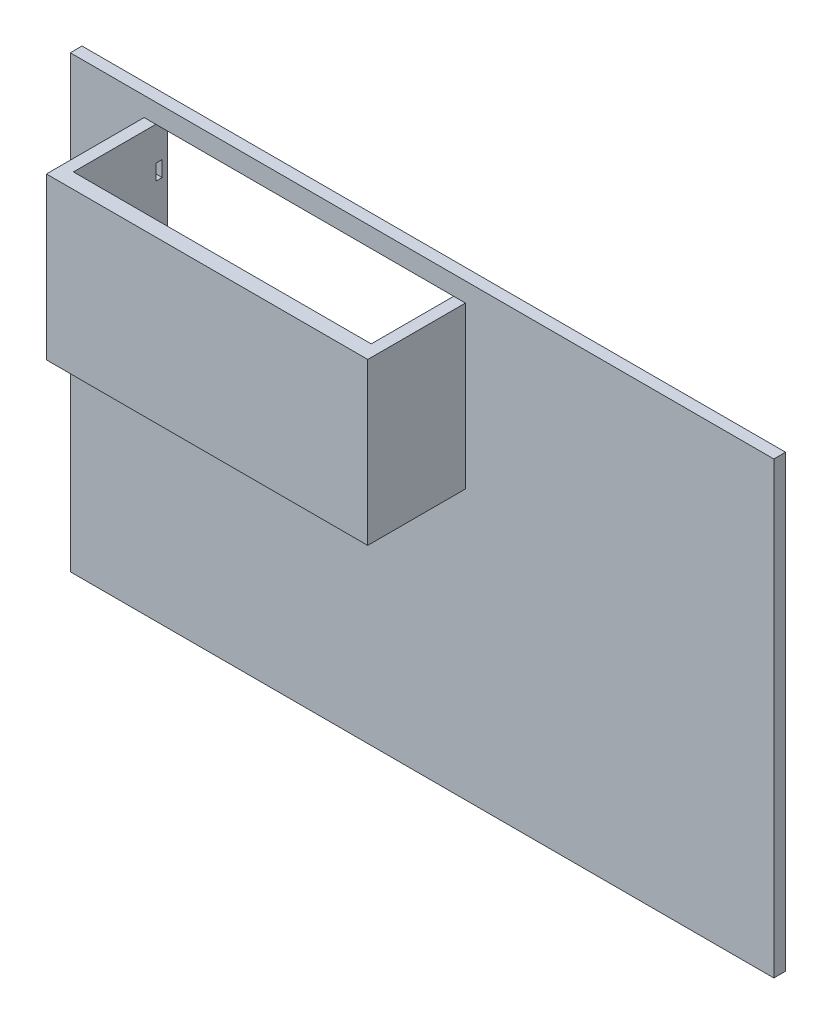
SolidWorks part; units mm, degrees
ref_plane "前视基准面" through (0, 0, 0) normal (0, 0, 1) x (1, 0, 0)
ref_plane "上视基准面" through (0, 0, 0) normal (0, 1, 0) x (1, 0, 0)
ref_plane "右视基准面" through (0, 0, 0) normal (1, 0, 0) x (0, 0, -1)
sketch "草图1" plane through (0, 0, 0) normal (0, 0, 1) x (1, 0, 0)
  line L1 (-90, 57.5) -> (90, 57.5)
  line L2 (-90, 57.5) -> (-90, -57.5)
  line L3 (-90, -57.5) -> (90, -57.5)
  line L4 (90, 57.5) -> (90, -57.5)
  line L5 (-90, 57.5) -> (90, -57.5) construction
  line L6 (-90, -57.5) -> (90, 57.5) construction
  point P0 (0, 0)
  dimension "D1" = 115
  dimension "D2" = 180
extrude "凸台-拉伸1" add sketch "草图1" along normal blind 3
sketch "草图7" plane through (0, 0, 0) normal (0, 0, -1) x (-1, 0, 0)
  line L0 (-90, 57.5) -> (90, 57.5) construction
  line L1 (-8.1, 52.6) -> (68.1, 52.6)
  line L2 (-8.1, 52.6) -> (-8.1, 11.4)
  line L3 (-8.1, 11.4) -> (68.1, 11.4)
  line L4 (68.1, 52.6) -> (68.1, 11.4)
  line L5 (90, 57.5) -> (90, -57.5) construction
  dimension "D1" = 41.2
  dimension "D2" = 76.2
  dimension "D3" = 4.9
  dimension "D4" = 21.9
extrude "电池位切除-拉伸3" cut sketch "草图7" against normal up to next
sketch "草图4" plane through (0, 0, 0) normal (0, 0, -1) x (-1, 0, 0)
  line L0 (68.1, 11.4) -> (68.1, 52.6) construction
  line L5 (68.1, 32) -> (94.8483, 32) construction
  line L10 (83.2374, -53.4277) -> (79.3374, -53.4277) construction
  line L11 (83.2374, -49.6277) -> (83.2374, -53.4277) construction
  line L12 (79.3374, -49.6277) -> (83.2374, -49.6277) construction
  line L13 (68.1, 20) -> (68.1, 24)
  line L20 (72.1, 20) -> (68.1, 20)
  line L21 (72.1, 24) -> (72.1, 20)
  line L22 (68.1, 24) -> (72.1, 24)
  line L29 (68.1, 40) -> (72.1, 40)
  line L30 (72.1, 40) -> (72.1, 44)
  line L31 (72.1, 44) -> (68.1, 44)
  line L32 (68.1, 44) -> (68.1, 40)
  point P6 (70.1, 40)
  dimension "D1" = 4
  dimension "D2" = 4
  dimension "D3" = 8
extrude "切除-拉伸2" cut sketch "草图4" along normal blind 1.6 from surface starting at face at (-30, 32, 3)
sketch "草图8" plane through (0, 0, 3) normal (0, 0, 1) x (1, 0, 0)
  line L0 (-68.1, 11.4) -> (-68.1, 20) construction
  line L1 (11.1, 11.4) -> (8.1, 11.4)
  line L2 (11.1, 11.4) -> (11.1, 52.6)
  line L3 (11.1, 52.6) -> (8.1, 52.6)
  line L4 (8.1, 11.4) -> (8.1, 52.6)
  line L5 (-68.1, 11.4) -> (-71.1, 11.4)
  line L6 (-68.1, 11.4) -> (-68.1, 52.6)
  line L7 (-68.1, 52.6) -> (-71.1, 52.6)
  line L8 (-71.1, 11.4) -> (-71.1, 52.6)
  line L9 (-68.1, 52.6) -> (8.1, 52.6) construction
  line L10 (8.1, 11.4) -> (-68.1, 11.4) construction
  line L11 (8.1, 52.6) -> (8.1, 11.4) construction
  dimension "D1" = 3
extrude "凸台-拉伸2" add sketch "草图8" along normal blind 25
sketch "草图9" plane through (0, 0, 28) normal (0, 0, 1) x (1, 0, 0)
  line L1 (11.1, 11.4) -> (-71.1, 11.4)
  line L2 (11.1, 11.4) -> (11.1, 52.6)
  line L3 (11.1, 52.6) -> (-71.1, 52.6)
  line L4 (-71.1, 11.4) -> (-71.1, 52.6)
extrude "凸台-拉伸3" add sketch "草图9" against normal blind 3.9
